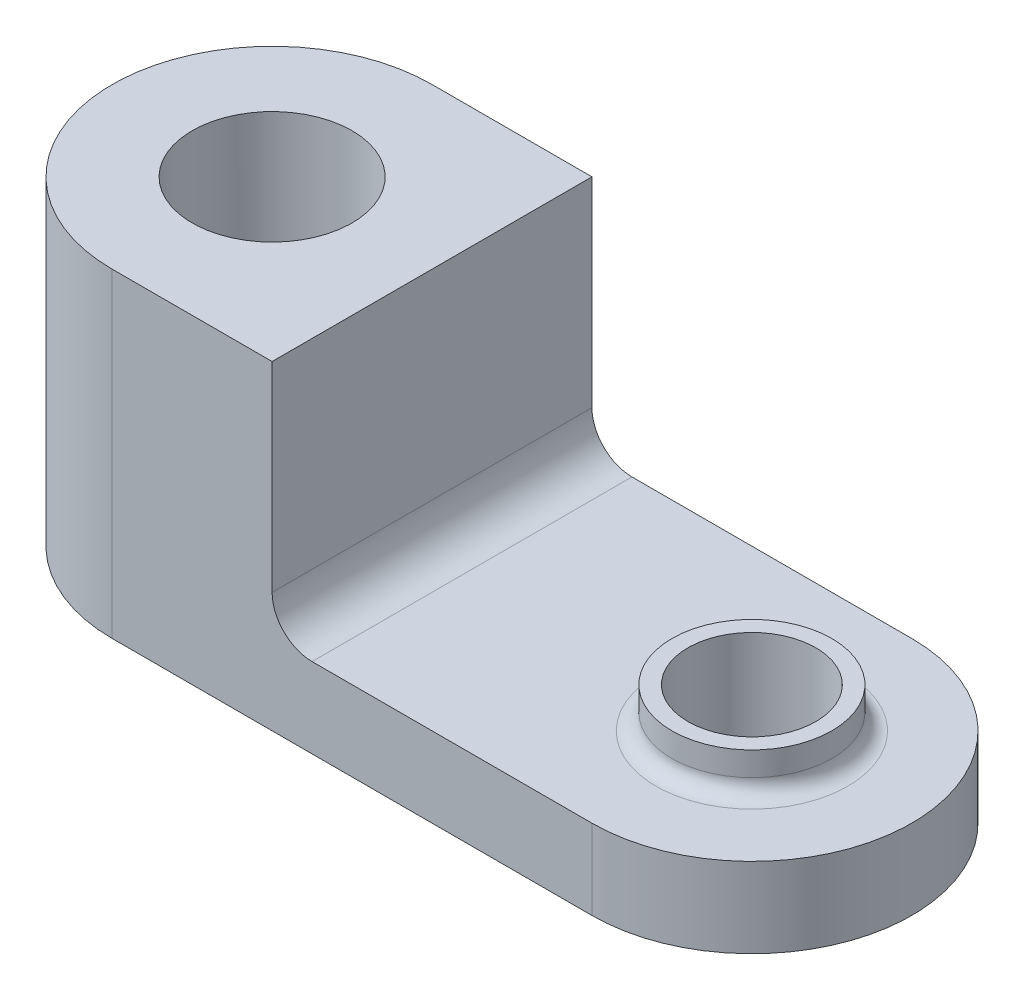
SolidWorks part; units mm, degrees
ref_plane "Front Plane" through (0, 0, 0) normal (0, 0, 1) x (1, 0, 0)
ref_plane "Top Plane" through (0, 0, 0) normal (0, 1, 0) x (1, 0, 0)
ref_plane "Right Plane" through (0, 0, 0) normal (1, 0, 0) x (0, 0, -1)
sketch "Sketch1" plane through (0, 0, 0) normal (0, 0, 1) x (1, 0, 0)
  line L0 (0, 0) -> (0, 40)
  line L1 (0, 40) -> (40, 40)
  line L2 (40, 40) -> (40, 10)
  line L3 (40, 10) -> (100, 10)
  line L4 (100, 10) -> (100, 0)
  line L5 (100, 0) -> (0, 0)
  dimension "D1" = 100
  dimension "D2" = 40
  dimension "D3" = 40
  dimension "D4" = 10
extrude "Boss-Extrude1" add sketch "Sketch1" along normal mid plane 40
fillet "Fillet7" 2 edges at (0, 20, -20) (0, 20, 20) type full round first side face at (46.6667, 16.6667, -20) second side face at (46.6667, 16.6667, 20) middle face at (0, 20, 0)
fillet "Fillet8" 2 edges at (100, 5, 20) (100, 5, -20) type full round first side face at (53.3333, 16.6667, 20) second side face at (53.3333, 16.6667, -20) middle face at (100, 5, 0)
fillet "Fillet9" radius 5 1 edges at (40, 10, 0)
sketch "Sketch2" plane through (0, 0, 0) normal (0, 1, 0) x (1, 0, 0)
  line L0 (40, -20) -> (40, 20) construction
  line L1 (40, -20) -> (20, -20) construction
  circle A0 centre (20, 0) radius 10
  circle A1 centre (80, 0) radius 8
  circle A2 centre (80, 0) radius 10
  point P9 (0, 0)
  point P10 (0, 0)
  dimension "D1" = 20
  dimension "D4" = 20
  dimension "D5" = 16
  dimension "D2" = 20
  dimension "D3" = 20
  dimension "D6" = 60
extrude "Cut-Extrude1" cut sketch "Sketch2" along normal up to next contours A0 | A1 | A0 region at (20, 0, 0) region at (80, 0, 0)
extrude "Boss-Extrude2" add sketch "Sketch2<4>" along normal blind 15 contours A2 A1 region at (70.2828, 0, 0)
sketch "Sketch2<4>" plane through (0, 0, 0) normal (0, 1, 0) x (1, 0, 0) same geometry as "Sketch2"
fillet "Fillet10" radius 2 1 edges at (80, 10, -10)
